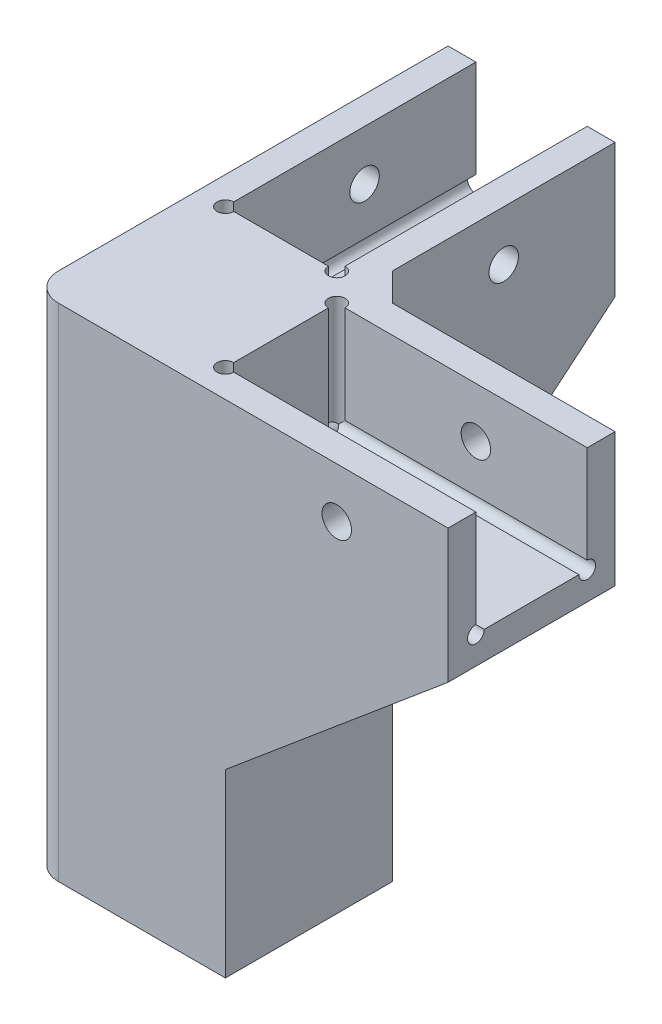
SolidWorks part; units mm, degrees
ref_plane "Front Plane" through (0, 0, 0) normal (0, 0, 1) x (1, 0, 0)
ref_plane "Top Plane" through (0, 0, 0) normal (0, 1, 0) x (1, 0, 0)
ref_plane "Right Plane" through (0, 0, 0) normal (1, 0, 0) x (0, 0, -1)
sketch "Sketch1" plane through (0, 0, 0) normal (0, 1, 0) x (1, 0, 0)
  line L1 (0, 0) -> (75, 0)
  line L2 (0, 0) -> (0, 75)
  line L3 (0, 75) -> (75, 75)
  line L4 (75, 0) -> (75, 75)
  dimension "D1" = 75
  dimension "D2" = 75
extrude "Boss-Extrude1" add sketch "Sketch1" along normal blind 90
sketch "Sketch2" plane through (0, 90, 0) normal (0, 1, 0) x (1, 0, 0)
  line L0 (75, 0) -> (75, 75) construction
  line L17 (75, 5) -> (30, 5)
  line L23 (75, 5) -> (75, 25)
  line L36 (75, 25) -> (30, 25)
  line L37 (30, 5) -> (30, 25)
  line L38 (75, 75) -> (0, 75) construction
  line L39 (5, 75) -> (25, 75)
  line L40 (5, 75) -> (5, 30)
  line L41 (5, 30) -> (25, 30)
  line L42 (25, 75) -> (25, 30)
  line L43 (0, 75) -> (0, 0) construction
  line L44 (0, 0) -> (75, 0) construction
  dimension "D1" = 20
  dimension "D2" = 45
  dimension "D3" = 5
  dimension "D4" = 5
  dimension "D5" = 20
  dimension "D6" = 45
extrude "Cut-Extrude2" cut sketch "Sketch2" against normal blind 19
sketch "Sketch3" plane through (0, 90, 0) normal (0, 1, 0) x (1, 0, 0)
  line L1 (75, 75) -> (30, 75)
  line L2 (75, 75) -> (75, 30)
  line L3 (75, 30) -> (30, 30)
  line L4 (30, 75) -> (30, 30)
  line L5 (75, 25) -> (30, 25) construction
  line L6 (25, 30) -> (25, 75) construction
  dimension "D1" = 5
  dimension "D2" = 5
extrude "Cut-Extrude3" cut sketch "Sketch3" against normal through all
sketch "Sketch4" plane through (0, 0, 0) normal (0, 0, 1) x (1, 0, 0)
  line L0 (35, 32.436) -> (35, 0)
  line L1 (0, 0) -> (75, 0) construction
  line L2 (35, 0) -> (75, 0)
  line L3 (75, 0) -> (75, 66)
  line L4 (75, 66) -> (35, 32.436)
  dimension "D1" = 40
  dimension "D2" = 66
  dimension "D3" = 50
extrude "Cut-Extrude4" cut sketch "Sketch4" against normal through all
sketch "Sketch5" plane through (30, 0, 0) normal (1, 0, 0) x (0, 0, -1)
  line L0 (35, 0) -> (35, 32.436)
  line L1 (75, 0) -> (30, 0) construction
  line L2 (35, 32.436) -> (75, 66)
  line L3 (75, 66) -> (75, 0)
  line L4 (75, 0) -> (35, 0)
  dimension "D1" = 66
  dimension "D2" = 50
  dimension "D3" = 40
extrude "Cut-Extrude5" cut sketch "Sketch5" against normal through all
fillet "Fillet1" radius 5 1 edges at (0, 45, 0)
sketch "Sketch7" plane through (0, 0, -30) normal (0, 0, -1) x (-1, 0, 0)
  line L0 (-30, 90) -> (-75, 90) construction
  line L1 (-75, 66) -> (-75, 90) construction
  circle A0 centre (-55, 81) radius 2.65
  dimension "D3" = 5.3
  dimension "D1" = 9
  dimension "D2" = 20
extrude "Cut-Extrude10" cut sketch "Sketch7" against normal through all both and the other way through all
sketch "Sketch8" plane through (30, 0, 0) normal (1, 0, 0) x (0, 0, -1)
  line L0 (75, 66) -> (75, 90) construction
  line L1 (75, 90) -> (30, 90) construction
  circle A0 centre (55, 81) radius 2.65
  dimension "D3" = 5.3
  dimension "D1" = 20
  dimension "D2" = 9
extrude "Cut-Extrude11" cut sketch "Sketch8" against normal through all both and the other way through all
sketch "Sketch9" plane through (0, 71, 0) normal (0, 1, 0) x (1, 0, 0)
  line L0 (25, 75) -> (5, 75) construction
  line L1 (75, 5) -> (75, 25) construction
  line L2 (30, 5) -> (75, 5) construction
  line L3 (25, 30) -> (25, 75) construction
  circle A0 centre (15, 55) radius 2.65
  circle A1 centre (55, 15) radius 2.65
  dimension "D3" = 5.3
  dimension "D4" = 5.3
  dimension "D1" = 20
  dimension "D2" = 20
  dimension "D5" = 10
  dimension "D6" = 10
extrude "Cut-Extrude12" cut sketch "Sketch9" against normal through all
ref_plane "Plane1" through (0, 66, 0) normal (0, 1, 0) x (1, 0, 0)
sketch "Sketch10" plane through (0, 66, 0) normal (0, 1, 0) x (1, 0, 0)
  circle A0 centre (55, 15) radius 5.5
  circle A1 centre (15, 55) radius 5.5
  dimension "D1" = 11
  dimension "D2" = 11
extrude "Cut-Extrude13" cut sketch "Sketch10" against normal through all
chamfer "Chamfer3" distance 5 angle 45 1 edges at (30, 45, -30)
sketch "Sketch11" plane through (0, 90, 0) normal (0, 1, 0) x (1, 0, 0)
  circle A0 centre (5, 30) radius 1.5
  circle A1 centre (25, 30) radius 1.5
  circle A2 centre (30, 25) radius 1.5
  circle A3 centre (30, 5) radius 1.5
  dimension "D1" = 3
extrude "Cut-Extrude14" cut sketch "Sketch11" against normal up to surface (19 mm away) up to face at (15, 71, -52.35)
sketch "Sketch12" plane through (75, 0, 0) normal (1, 0, 0) x (0, 0, -1)
  circle A0 centre (5, 71) radius 1.5
  circle A1 centre (25, 71) radius 1.5
  dimension "D1" = 3
extrude "Cut-Extrude15" cut sketch "Sketch12" against normal up to surface (45 mm away) up to face at (30, 80.5, -15)
sketch "Sketch13" plane through (0, 0, -75) normal (0, 0, -1) x (-1, 0, 0)
  circle A0 centre (-25, 71) radius 1.5
  circle A1 centre (-5, 71) radius 1.5
  dimension "D1" = 3
extrude "Cut-Extrude16" cut sketch "Sketch13" against normal up to surface (45 mm away) up to face at (15, 80.5, -30)
fillet "Fillet2" radius 3 4 edges at (5, 71, -30) (25, 71, -30) (30, 71, -25) (30, 71, -5)
